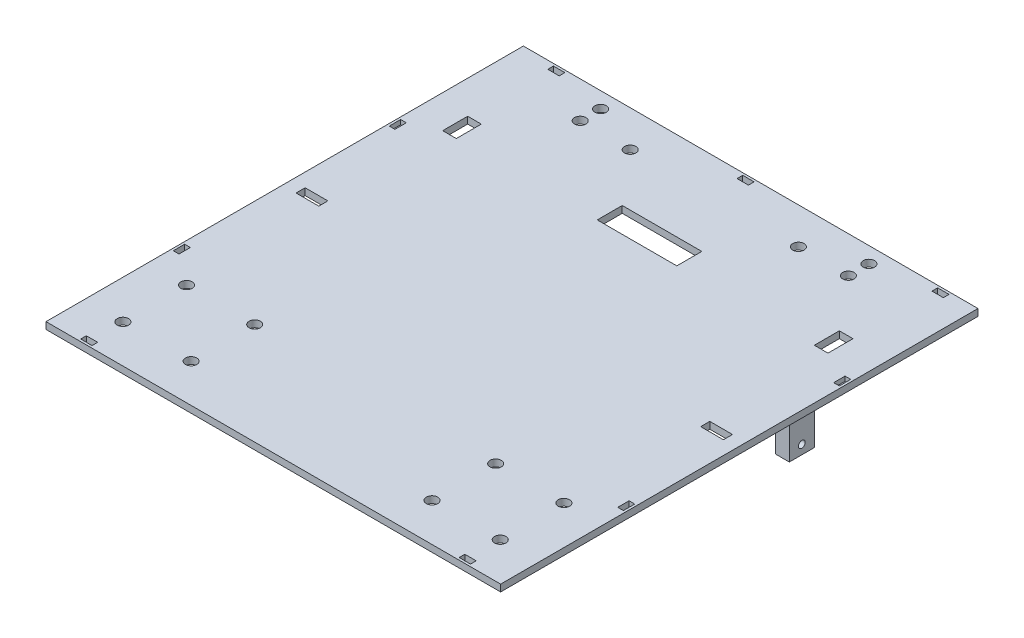
SolidWorks part; units mm, degrees
material "ABS"
ref_plane "Front Plane" through (0, 0, 0) normal (0, 0, 1) x (1, 0, 0)
ref_plane "Top Plane" through (0, 0, 0) normal (0, 1, 0) x (1, 0, 0)
ref_plane "Right Plane" through (0, 0, 0) normal (1, 0, 0) x (0, 0, -1)
sketch "Sketch1" plane through (0, 0, 0) normal (0, 1, 0) x (1, 0, 0)
  line L1 (100, 105) -> (-100, 105)
  line L2 (100, 105) -> (100, -105)
  line L3 (100, -105) -> (-100, -105)
  line L4 (-100, 105) -> (-100, -105)
  line L5 (100, 105) -> (-100, -105) construction
  line L6 (100, -105) -> (-100, 105) construction
  line L11 (94, 3) -> (84, 3)
  line L12 (94, 3) -> (94, -1)
  line L13 (94, -1) -> (84, -1)
  line L14 (84, 3) -> (84, -1)
  line L15 (94, 3) -> (84, -1) construction
  line L16 (94, -1) -> (84, 3) construction
  line L17 (-94, -1) -> (-84, -1)
  line L18 (-94, -1) -> (-94, 3)
  line L19 (-94, 3) -> (-84, 3)
  line L20 (-84, -1) -> (-84, 3)
  line L21 (-94, -1) -> (-84, 3) construction
  line L22 (-94, 3) -> (-84, -1) construction
  line L23 (-85.5, 38) -> (-79.5, 38)
  line L24 (-85.5, 38) -> (-85.5, 49)
  line L25 (-85.5, 49) -> (-79.5, 49)
  line L26 (-79.5, 38) -> (-79.5, 49)
  line L27 (-85.5, 38) -> (-79.5, 49) construction
  line L28 (-85.5, 49) -> (-79.5, 38) construction
  line L29 (78, 38) -> (84, 38)
  line L30 (78, 38) -> (78, 49)
  line L31 (78, 49) -> (84, 49)
  line L32 (84, 38) -> (84, 49)
  line L33 (78, 38) -> (84, 49) construction
  line L34 (78, 49) -> (84, 38) construction
  line L35 (85.75, -104) -> (80.75, -104)
  line L36 (85.75, -104) -> (85.75, -101.5)
  line L37 (85.75, -101.5) -> (80.75, -101.5)
  line L38 (80.75, -104) -> (80.75, -101.5)
  line L39 (85.75, -104) -> (80.75, -101.5) construction
  line L40 (85.75, -101.5) -> (80.75, -104) construction
  line L41 (-2.5, 101.5) -> (2.5, 101.5)
  line L42 (-2.5, 101.5) -> (-2.5, 104)
  line L43 (-2.5, 104) -> (2.5, 104)
  line L44 (2.5, 101.5) -> (2.5, 104)
  line L45 (-2.5, 101.5) -> (2.5, 104) construction
  line L46 (-2.5, 104) -> (2.5, 101.5) construction
  line L47 (-85.75, -104) -> (-80.75, -104)
  line L48 (-85.75, -104) -> (-85.75, -101.5)
  line L49 (-85.75, -101.5) -> (-80.75, -101.5)
  line L50 (-80.75, -104) -> (-80.75, -101.5)
  line L51 (-85.75, -104) -> (-80.75, -101.5) construction
  line L52 (-85.75, -101.5) -> (-80.75, -104) construction
  line L53 (-80.75, 104) -> (-85.75, 104)
  line L54 (-80.75, 104) -> (-80.75, 101.5)
  line L55 (-80.75, 101.5) -> (-85.75, 101.5)
  line L56 (-85.75, 104) -> (-85.75, 101.5)
  line L57 (-80.75, 104) -> (-85.75, 101.5) construction
  line L58 (-80.75, 101.5) -> (-85.75, 104) construction
  line L59 (83.25, 101.5) -> (88.25, 101.5)
  line L60 (83.25, 101.5) -> (83.25, 104)
  line L61 (83.25, 104) -> (88.25, 104)
  line L62 (88.25, 101.5) -> (88.25, 104)
  line L63 (83.25, 101.5) -> (88.25, 104) construction
  line L64 (83.25, 104) -> (88.25, 101.5) construction
  line L65 (99, -45) -> (96.5, -45)
  line L66 (99, -45) -> (99, -50)
  line L67 (99, -50) -> (96.5, -50)
  line L68 (96.5, -45) -> (96.5, -50)
  line L69 (99, -45) -> (96.5, -50) construction
  line L70 (99, -50) -> (96.5, -45) construction
  line L71 (99, 50) -> (96.5, 50)
  line L72 (99, 50) -> (99, 45)
  line L73 (99, 45) -> (96.5, 45)
  line L74 (96.5, 50) -> (96.5, 45)
  line L75 (99, 50) -> (96.5, 45) construction
  line L76 (99, 45) -> (96.5, 50) construction
  line L77 (-99, -45) -> (-96.5, -45)
  line L78 (-99, -45) -> (-99, -50)
  line L79 (-99, -50) -> (-96.5, -50)
  line L80 (-96.5, -45) -> (-96.5, -50)
  line L81 (-99, -45) -> (-96.5, -50) construction
  line L82 (-99, -50) -> (-96.5, -45) construction
  line L83 (-99, 45) -> (-96.5, 45)
  line L84 (-99, 45) -> (-99, 50)
  line L85 (-99, 50) -> (-96.5, 50)
  line L86 (-96.5, 45) -> (-96.5, 50)
  line L87 (-99, 45) -> (-96.5, 50) construction
  line L88 (-99, 50) -> (-96.5, 45) construction
  line L89 (84, 55) -> (78, 55)
  line L90 (84, 55) -> (84, 66)
  line L91 (84, 66) -> (78, 66)
  line L92 (78, 55) -> (78, 66)
  line L93 (-79.5, 55) -> (-85.5, 55)
  line L94 (-79.5, 55) -> (-79.5, 66)
  line L95 (-79.5, 66) -> (-85.5, 66)
  line L96 (-85.5, 55) -> (-85.5, 66)
  line L97 (-17.5, 66) -> (17.5, 66)
  line L98 (-17.5, 66) -> (-17.5, 55)
  line L99 (-17.5, 55) -> (17.5, 55)
  line L100 (17.5, 66) -> (17.5, 55)
  circle A0 centre (-59, 98) radius 2.5
  circle A1 centre (-59, 89) radius 2.5
  circle A2 centre (-37, 89) radius 2.5
  circle A3 centre (59, 98) radius 2.5
  circle A4 centre (59, 89) radius 2.5
  circle A5 centre (37, 89) radius 2.5
  circle A6 centre (83, -88.1753) radius 2.5
  circle A7 centre (83, -60.1753) radius 2.4959
  circle A8 centre (53, -88.1753) radius 2.5
  circle A9 centre (53, -60.1753) radius 2.5
  circle A10 centre (-83, -88.1753) radius 2.5
  circle A11 centre (-53, -88.1753) radius 2.5
  circle A12 centre (-53, -60.1753) radius 2.5
  circle A13 centre (-83, -60.1753) radius 2.5
  point P0 (0, 0)
  point P6 (89, 1)
  point P23 (-89, 1)
  point P28 (-82.5, 43.5)
  point P33 (81, 43.5)
  point P38 (83.25, -102.75)
  point P43 (0, 102.75)
  point P48 (-83.25, -102.75)
  point P53 (-83.25, 102.75)
  point P58 (85.75, 102.75)
  point P59 (97.75, -47.5)
  point P68 (97.75, -45)
  point P69 (97.75, 47.5)
  point P74 (-97.75, -47.5)
  point P79 (-97.75, 47.5)
  point P112 (0, 0)
  point P113 (0, 0)
  point P114 (0, 0)
  point P115 (-53, -60.1753)
  dimension "D7" = 16
  dimension "D8" = 63
  dimension "D9" = 16
  dimension "D11" = 7
  dimension "D13" = 41
  dimension "D15" = 63
  dimension "D17" = 10
  dimension "D79" = 28
  dimension "D80" = 30
  dimension "D82" = 28
  dimension "D83" = 30
  dimension "D1" = 200
  dimension "D2" = 210
  dimension "D3" = 41
  dimension "D4" = 41
  dimension "D5" = 7
  dimension "D6" = 104
  dimension "D10" = 16
  dimension "D12" = 16
  dimension "D14" = 41
  dimension "D16" = 6
  dimension "D18" = 4
  dimension "D19" = 104
  dimension "D20" = 6
  dimension "D21" = 4
  dimension "D22" = 10
  dimension "D23" = 56
  dimension "D24" = 14.5
  dimension "D25" = 11
  dimension "D26" = 6
  dimension "D27" = 56
  dimension "D28" = 6
  dimension "D29" = 11
  dimension "D30" = 16
  dimension "D31" = 14.25
  dimension "D32" = 1
  dimension "D33" = 5
  dimension "D34" = 2.5
  dimension "D35" = 1
  dimension "D36" = 100
  dimension "D37" = 5
  dimension "D38" = 2.5
  dimension "D39" = 1
  dimension "D40" = 14.25
  dimension "D41" = 5
  dimension "D42" = 2.5
  dimension "D43" = 14.25
  dimension "D44" = 1
  dimension "D45" = 5
  dimension "D46" = 2.5
  dimension "D47" = 14.25
  dimension "D48" = 1
  dimension "D49" = 5
  dimension "D50" = 2.5
  dimension "D51" = 1
  dimension "D52" = 5
  dimension "D53" = 2.5
  dimension "D54" = 55
  dimension "D55" = 55
  dimension "D56" = 1
  dimension "D57" = 5
  dimension "D58" = 2.5
  dimension "D59" = 1
  dimension "D60" = 55
  dimension "D61" = 2.5
  dimension "D62" = 5
  dimension "D63" = 55
  dimension "D64" = 1
  dimension "D65" = 2.5
  dimension "D66" = 5
  dimension "D67" = 16
  dimension "D68" = 11
  dimension "D69" = 6
  dimension "D70" = 39
  dimension "D71" = 14.5
  dimension "D72" = 39
  dimension "D73" = 11
  dimension "D74" = 6
  dimension "D75" = 39
  dimension "D76" = 82.5
  dimension "D77" = 35
  dimension "D78" = 11
  dimension "D81" = 17
  dimension "D84" = 17
extrude "MainBody" add sketch "Sketch1" along normal blind 1 contours L83 L86 L85 L84 | L71 L74 L73 L72 region at (97.75, 0, -47.5) region at (-97.75, 0, -47.5)
extrude "SayapRoda" add sketch "Sketch1<4>" against normal blind 30 and the other way blind 3 separate body contours L23 L26 L25 L24 | L29 L32 L31 L30 region at (-82.5, 0, -43.5) region at (81, 0, -43.5)
sketch "Sketch1<4>" plane through (0, 0, 0) normal (0, 1, 0) x (1, 0, 0) same geometry as "Sketch1"
hole_wizard "Hole1" positions "3DSketch2" profile "Sketch9" legacy end condition through all
sketch3d "3DSketch2"
  line L0 (84, 3, -49) -> (84, -30, -49) construction
  line L1 (84, -30, -38) -> (84, -30, -49) construction
  point P0 (84, -26, -43.5)
  point P2 (84, -9.0002, -43.4154)
  point P4 (84, -7.7287, -43.5)
  point P6 (84, -6.2408, -43.5)
  point P8 (84, -4.8783, -43.5)
  point P13 (0, 0, 0)
  dimension "D1" = 17
  dimension "D2" = 5.5
  dimension "D3" = 5.5
  dimension "D4" = 5.5
  dimension "D5" = 5.5
  dimension "D6" = 4
sketch "Sketch9" plane through (84, -26, -43.5) normal (0, 1, 0) x (0, 0, -1)
  line L0 (0, 0) -> (0, 183)
  line L1 (0, 183) -> (1.5, 183)
  line L2 (1.5, 183) -> (1.5, 0)
  line L3 (1.5, 0) -> (0, 0)
  line L4 (0, 110) -> (0, -10) construction
  dimension "Diameter" = 3
  dimension "Depth" = 183
extrude "Boss-Extrude1" add sketch "Sketch1<7>" along normal blind 3
sketch "Sketch1<7>" plane through (0, 0, 0) normal (0, 1, 0) x (1, 0, 0) same geometry as "Sketch1"
